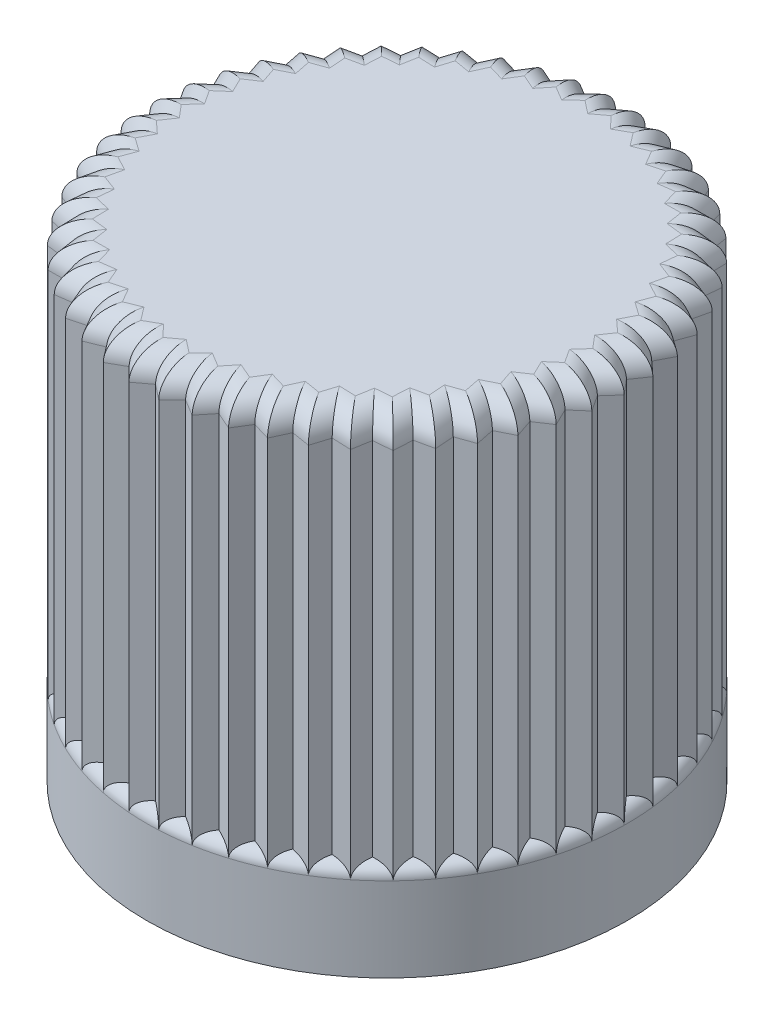
SolidWorks part; units mm, degrees
ref_plane "Спереди" through (0, 0, 0) normal (0, 0, 1) x (1, 0, 0)
ref_plane "Сверху" through (0, 0, 0) normal (0, 1, 0) x (1, 0, 0)
ref_plane "Справа" through (0, 0, 0) normal (1, 0, 0) x (0, 0, -1)
sketch "Sketch1" plane through (0, 0, 0) normal (0, 1, 0) x (1, 0, 0)
  circle A0 centre (0, 0) radius 10
  dimension "D1" = 20
extrude "Boss-Extrude1" add sketch "Sketch1" along normal blind 20
sketch "Sketch2" plane through (0, 0, 0) normal (0, -1, 0) x (1, 0, 0)
  circle A0 centre (0, 0) radius 3.125
  dimension "D1" = 6.25
extrude "Cut-Extrude1" cut sketch "Sketch2" against normal blind 17
sketch "Sketch3" plane through (0, 0, 0) normal (0, -1, 0) x (1, 0, 0)
  circle A0 centre (0, 0) radius 6
  dimension "D1" = 12
extrude "Cut-Extrude2" cut sketch "Sketch3" against normal blind 4
sketch "Sketch4" plane through (0, 20, 0) normal (0, 1, 0) x (1, 0, 0)
  line L0 (9.3072, -1.9044) -> (9.6518, -2.6158)
  line L1 (9.6518, -2.6158) -> (8.9951, -3.0559)
  line L2 (8.9951, -3.0559) -> (9.2478, -3.8049)
  line L3 (9.2478, -3.8049) -> (8.5411, -4.1592)
  line L4 (8.5411, -4.1592) -> (8.698, -4.934)
  line L5 (8.698, -4.934) -> (7.9525, -5.1969)
  line L6 (7.9525, -5.1969) -> (8.0111, -5.9852)
  line L7 (8.0111, -5.9852) -> (7.2385, -6.1526)
  line L8 (7.2385, -6.1526) -> (7.1977, -6.9421)
  line L9 (7.1977, -6.9421) -> (6.4103, -7.0113)
  line L10 (6.4103, -7.0113) -> (6.2709, -7.7895)
  line L11 (6.2709, -7.7895) -> (5.481, -7.7594)
  line L12 (5.481, -7.7594) -> (5.2452, -8.514)
  line L13 (5.2452, -8.514) -> (4.4652, -8.3852)
  line L14 (4.4652, -8.3852) -> (4.1367, -9.1042)
  line L15 (4.1367, -9.1042) -> (3.3791, -8.8787)
  line L16 (3.3791, -8.8787) -> (2.9631, -9.5509)
  line L17 (2.9631, -9.5509) -> (2.2396, -9.2322)
  line L18 (2.2396, -9.2322) -> (1.7426, -9.847)
  line L19 (1.7426, -9.847) -> (1.0649, -9.4401)
  line L20 (1.0649, -9.4401) -> (0.4948, -9.9878)
  line L21 (0.4948, -9.9878) -> (-0.1267, -9.4992)
  line L22 (-0.1267, -9.4992) -> (-0.7609, -9.971)
  line L23 (-0.7609, -9.971) -> (-1.3163, -9.4084)
  line L24 (-1.3163, -9.4084) -> (-2.0046, -9.797)
  line L25 (-2.0046, -9.797) -> (-2.4851, -9.1692)
  line L26 (-2.4851, -9.1692) -> (-3.2167, -9.4685)
  line L27 (-3.2167, -9.4685) -> (-3.6147, -8.7855)
  line L28 (-3.6147, -8.7855) -> (-4.3781, -8.9907)
  line L29 (-4.3781, -8.9907) -> (-4.6873, -8.2631)
  line L30 (-4.6873, -8.2631) -> (-5.4704, -8.3711)
  line L31 (-5.4704, -8.3711) -> (-5.686, -7.6105)
  line L32 (-5.686, -7.6105) -> (-6.4764, -7.6194)
  line L33 (-6.4764, -7.6194) -> (-6.595, -6.8379)
  line L34 (-6.595, -6.8379) -> (-7.3803, -6.7476)
  line L35 (-7.3803, -6.7476) -> (-7.4, -5.9574)
  line L36 (-7.4, -5.9574) -> (-8.1678, -5.7694)
  line L37 (-8.1678, -5.7694) -> (-8.0883, -4.9829)
  line L38 (-8.0883, -4.9829) -> (-8.8265, -4.7002)
  line L39 (-8.8265, -4.7002) -> (-8.649, -3.9299)
  line L40 (-8.649, -3.9299) -> (-9.346, -3.5569)
  line L41 (-9.346, -3.5569) -> (-9.0734, -2.8149)
  line L42 (-9.0734, -2.8149) -> (-9.7181, -2.3575)
  line L43 (-9.7181, -2.3575) -> (-9.3546, -1.6555)
  line L44 (-9.3546, -1.6555) -> (-9.937, -1.1209)
  line L45 (-9.937, -1.1209) -> (-9.4884, -0.47)
  line L46 (-9.4884, -0.47) -> (-9.9991, 0.1334)
  line L47 (-9.9991, 0.1334) -> (-9.4725, 0.7229)
  line L48 (-9.4725, 0.7229) -> (-9.9036, 1.3855)
  line L49 (-9.9036, 1.3855) -> (-9.3072, 1.9044)
  line L50 (-9.3072, 1.9044) -> (-9.6518, 2.6158)
  line L51 (-9.6518, 2.6158) -> (-8.9951, 3.0559)
  line L52 (-8.9951, 3.0559) -> (-9.2478, 3.8049)
  line L53 (-9.2478, 3.8049) -> (-8.5411, 4.1592)
  line L54 (-8.5411, 4.1592) -> (-8.698, 4.934)
  line L55 (-8.698, 4.934) -> (-7.9525, 5.1969)
  line L56 (-7.9525, 5.1969) -> (-8.0111, 5.9852)
  line L57 (-8.0111, 5.9852) -> (-7.2385, 6.1526)
  line L58 (-7.2385, 6.1526) -> (-7.1977, 6.9421)
  line L59 (-7.1977, 6.9421) -> (-6.4103, 7.0113)
  line L60 (-6.4103, 7.0113) -> (-6.2709, 7.7895)
  line L61 (-6.2709, 7.7895) -> (-5.481, 7.7594)
  line L62 (-5.481, 7.7594) -> (-5.2452, 8.514)
  line L63 (-5.2452, 8.514) -> (-4.4652, 8.3852)
  line L64 (-4.4652, 8.3852) -> (-4.1367, 9.1042)
  line L65 (-4.1367, 9.1042) -> (-3.3791, 8.8787)
  line L66 (-3.3791, 8.8787) -> (-2.9631, 9.5509)
  line L67 (-2.9631, 9.5509) -> (-2.2396, 9.2322)
  line L68 (-2.2396, 9.2322) -> (-1.7426, 9.847)
  line L69 (-1.7426, 9.847) -> (-1.0649, 9.4401)
  line L70 (-1.0649, 9.4401) -> (-0.4948, 9.9878)
  line L71 (-0.4948, 9.9878) -> (0.1267, 9.4992)
  line L72 (0.1267, 9.4992) -> (0.7609, 9.971)
  line L73 (0.7609, 9.971) -> (1.3163, 9.4084)
  line L74 (1.3163, 9.4084) -> (2.0046, 9.797)
  line L75 (2.0046, 9.797) -> (2.4851, 9.1692)
  line L76 (2.4851, 9.1692) -> (3.2167, 9.4685)
  line L77 (3.2167, 9.4685) -> (3.6147, 8.7855)
  line L78 (3.6147, 8.7855) -> (4.3781, 8.9907)
  line L79 (4.3781, 8.9907) -> (4.6873, 8.2631)
  line L80 (4.6873, 8.2631) -> (5.4704, 8.3711)
  line L81 (5.4704, 8.3711) -> (5.686, 7.6105)
  line L82 (5.686, 7.6105) -> (6.4764, 7.6194)
  line L83 (6.4764, 7.6194) -> (6.595, 6.8379)
  line L84 (6.595, 6.8379) -> (7.3803, 6.7476)
  line L85 (7.3803, 6.7476) -> (7.4, 5.9574)
  line L86 (7.4, 5.9574) -> (8.1678, 5.7694)
  line L87 (8.1678, 5.7694) -> (8.0883, 4.9829)
  line L88 (8.0883, 4.9829) -> (8.8265, 4.7002)
  line L89 (8.8265, 4.7002) -> (8.649, 3.9299)
  line L90 (8.649, 3.9299) -> (9.346, 3.5569)
  line L91 (9.346, 3.5569) -> (9.0734, 2.8149)
  line L92 (9.0734, 2.8149) -> (9.7181, 2.3575)
  line L93 (9.7181, 2.3575) -> (9.3546, 1.6555)
  line L94 (9.3546, 1.6555) -> (9.937, 1.1209)
  line L95 (9.937, 1.1209) -> (9.4884, 0.47)
  line L96 (9.4884, 0.47) -> (9.9991, -0.1334)
  line L97 (9.9991, -0.1334) -> (9.4725, -0.7229)
  line L98 (9.4725, -0.7229) -> (9.9036, -1.3855)
  line L99 (9.9036, -1.3855) -> (9.3072, -1.9044)
  circle A0 centre (0, 0) radius 9.5 construction
  circle A1 centre (0, 0) radius 10 construction
  point P7 (0, 0)
  point P9 (0, 0)
  point P158 (0, 0)
  dimension "D1" = 0.5
  dimension "D2" = 50
extrude "Cut-Extrude4" cut sketch "Sketch4" against normal blind 16 flip side to cut
fillet "Fillet1" radius 0.5 50 edges at (9.971, 4, 0.7609) (9.797, 4, 2.0046) (9.4685, 4, 3.2167) (8.9907, 4, 4.3781) (8.3711, 4, 5.4704) (7.6194, 4, 6.4764) (6.7476, 4, 7.3803) (5.7694, 4, 8.1678) (4.7002, 4, 8.8265) (3.5569, 4, 9.346) (2.3575, 4, 9.7181) (1.1209, 4, 9.937) (-0.1334, 4, 9.9991) (-1.3855, 4, 9.9036) (-2.6158, 4, 9.6518) (-3.8049, 4, 9.2478) (-4.934, 4, 8.698) (-5.9852, 4, 8.0111) (-6.9421, 4, 7.1977) (-7.7895, 4, 6.2709) (-8.514, 4, 5.2452) (-9.1042, 4, 4.1367) (-9.5509, 4, 2.9631) (-9.847, 4, 1.7426) (-9.9878, 4, 0.4948) (-9.971, 4, -0.7609) (-9.797, 4, -2.0046) (-9.4685, 4, -3.2167) (-8.9907, 4, -4.3781) (-8.3711, 4, -5.4704) (-7.6194, 4, -6.4764) (-6.7476, 4, -7.3803) (-5.7694, 4, -8.1678) (-4.7002, 4, -8.8265) (-3.5569, 4, -9.346) (-2.3575, 4, -9.7181) (-1.1209, 4, -9.937) (0.1334, 4, -9.9991) (1.3855, 4, -9.9036) (2.6158, 4, -9.6518) (3.8049, 4, -9.2478) (4.934, 4, -8.698) (5.9852, 4, -8.0111) (6.9421, 4, -7.1977) (7.7895, 4, -6.2709) (8.514, 4, -5.2452) (9.1042, 4, -4.1367) (9.5509, 4, -2.9631) (9.847, 4, -1.7426) (9.9878, 4, -0.4948)
fillet "Fillet2" radius 1 100 edges at (9.3234, 20, 2.8359) (9.1215, 20, 3.4304) (8.8945, 20, 3.982) (8.6196, 20, 4.5466) (8.3253, 20, 5.0654) (7.9818, 20, 5.591) (7.6248, 20, 6.0689) (7.2181, 20, 6.5473) (6.804, 20, 6.9767) (6.3406, 20, 7.4004) (5.8759, 20, 7.7744) (5.3631, 20, 8.1367) (4.8552, 20, 8.4496) (4.301, 20, 8.7447) (3.7579, 20, 8.9915) (3.1711, 20, 9.2148) (2.6013, 20, 9.3916) (1.9911, 20, 9.5396) (1.4038, 20, 9.6436) (0.7798, 20, 9.7139) (0.184, 20, 9.7435) (-0.4438, 20, 9.7351) (-1.0386, 20, 9.6897) (-1.6604, 20, 9.6027) (-2.2449, 20, 9.4831) (-2.8509, 20, 9.3189) (-3.4157, 20, 9.127) (-3.9964, 20, 8.8881) (-4.5327, 20, 8.6269) (-5.0788, 20, 8.3171) (-5.5782, 20, 7.9908) (-6.0812, 20, 7.615) (-6.5357, 20, 7.2286) (-6.9877, 20, 6.7928) (-7.3902, 20, 6.3525) (-7.7839, 20, 5.8634) (-8.1281, 20, 5.3762) (-8.4574, 20, 4.8416) (-8.7378, 20, 4.3151) (-8.9975, 20, 3.7434) (-9.2097, 20, 3.1859) (-9.3958, 20, 2.5862) (-9.5364, 20, 2.0065) (-9.6458, 20, 1.3882) (-9.7127, 20, 0.7955) (-9.7437, 20, 0.1683) (-9.7358, 20, -0.4281) (-9.688, 20, -1.0542) (-9.6054, 20, -1.645) (-9.4795, 20, -2.2601) (-9.3234, 20, -2.8359) (-9.1215, 20, -3.4304) (-8.8945, 20, -3.982) (-8.6196, 20, -4.5466) (-8.3253, 20, -5.0654) (-7.9818, 20, -5.591) (-7.6248, 20, -6.0689) (-7.2181, 20, -6.5473) (-6.804, 20, -6.9767) (-6.3406, 20, -7.4004) (-5.8759, 20, -7.7744) (-5.3631, 20, -8.1367) (-4.8552, 20, -8.4496) (-4.301, 20, -8.7447) (-3.7579, 20, -8.9915) (-3.1711, 20, -9.2148) (-2.6013, 20, -9.3916) (-1.9911, 20, -9.5396) (-1.4038, 20, -9.6436) (-0.7798, 20, -9.7139) (-0.184, 20, -9.7435) (0.4438, 20, -9.7351) (1.0386, 20, -9.6897) (1.6604, 20, -9.6027) (2.2449, 20, -9.4831) (2.8509, 20, -9.3189) (3.4157, 20, -9.127) (3.9964, 20, -8.8881) (4.5327, 20, -8.6269) (5.0788, 20, -8.3171) (5.5782, 20, -7.9908) (6.0812, 20, -7.615) (6.5357, 20, -7.2286) (6.9877, 20, -6.7928) (7.3902, 20, -6.3525) (7.7839, 20, -5.8634) (8.1281, 20, -5.3762) (8.4574, 20, -4.8416) (8.7378, 20, -4.3151) (8.9975, 20, -3.7434) (9.2097, 20, -3.1859) (9.3958, 20, -2.5862) (9.5364, 20, -2.0065) (9.6458, 20, -1.3882) (9.7127, 20, -0.7955) (9.7437, 20, -0.1683) (9.7358, 20, 0.4281) (9.688, 20, 1.0542) (9.6054, 20, 1.645) (9.4795, 20, 2.2601)
